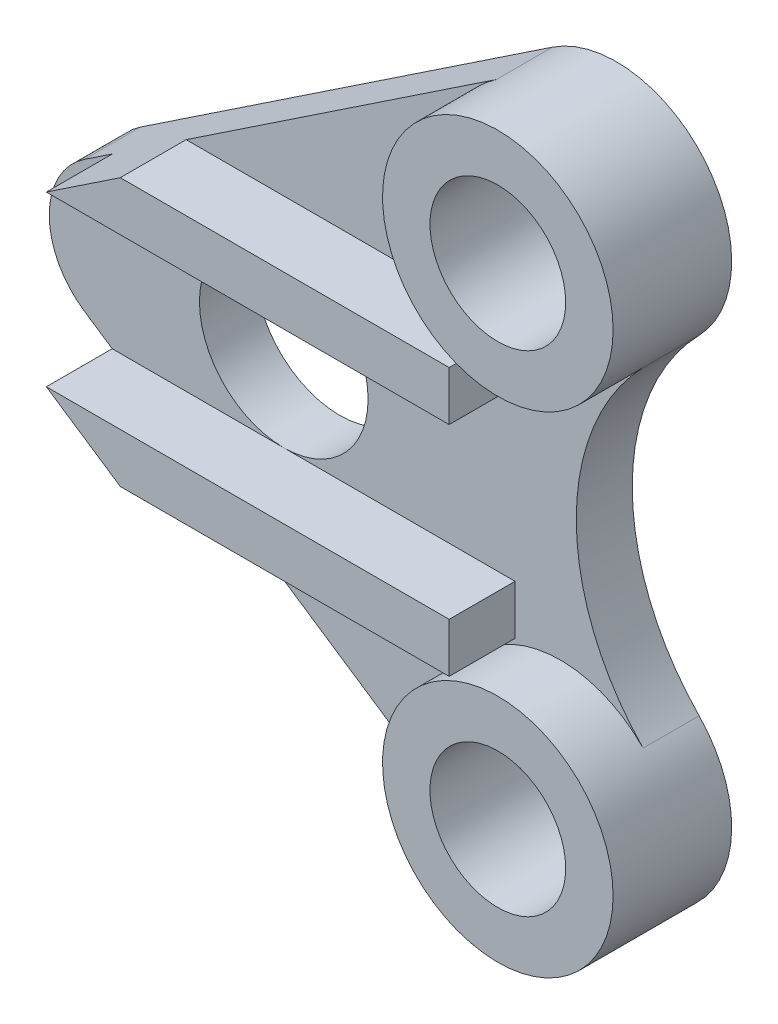
SolidWorks part; units mm, degrees
ref_plane "Front Plane" through (0, 0, 0) normal (0, 0, 1) x (1, 0, 0)
ref_plane "Top Plane" through (0, 0, 0) normal (0, 1, 0) x (1, 0, 0)
ref_plane "Right Plane" through (0, 0, 0) normal (1, 0, 0) x (0, 0, -1)
sketch "Sketch1" plane through (0, 0, 0) normal (0, 0, 1) x (1, 0, 0)
  line L0 (0, 5.1219) -> (0, -5.1219) construction
  line L1 (0, 0) -> (13.2766, 0) construction
  line L2 (8.1971, 13.145) -> (-7.6874, 2.5346)
  line L3 (-7.6874, -2.5346) -> (8.1971, -13.145)
  circle A0 centre (0, 0) radius 3.2512
  circle A1 centre (-5.9944, 0) radius 1.4732 construction
  circle A2 centre (5.9944, 0) radius 1.4732 construction
  circle A3 centre (10.6661, 9.4488) radius 2.6162
  circle A4 centre (10.6661, -9.4488) radius 2.6162
  arc A5 (-7.6874, 2.5346) -> (-7.6874, -2.5346) centre (-5.9944, 0) ccw
  arc A6 (8.1971, -13.145) -> (13.8546, -6.3518) centre (10.6661, -9.4488) ccw
  arc A7 (13.8546, 6.3518) -> (8.1971, 13.145) centre (10.6661, 9.4488) ccw
  arc A8 (13.8546, 6.3518) -> (13.8546, -6.3518) centre (20.3941, 0) ccw
  point P9 (0, 0)
  dimension "D1" = 2.9464
  dimension "D2" = 6.5024
  dimension "D3" = 9.0424
  dimension "D4" = 5.2324
  dimension "D5" = 18.8976
  dimension "D6" = 8.382
  dimension "D7" = 4.445
  dimension "D8" = 3.048
  dimension "D9" = 3.81
extrude "Boss-Extrude1" add sketch "Sketch1" along normal blind 4.572
sketch "Sketch2" plane through (0, 0, 4.572) normal (0, 0, 1) x (1, 0, 0)
  line L2 (8.1971, 13.145) -> (-7.6874, 2.5346)
  line L3 (-7.6874, -2.5346) -> (8.1971, -13.145)
  line L4 (8.1971, 13.145) -> (-7.6874, 2.5346)
  line L5 (-7.6874, -2.5346) -> (8.1971, -13.145)
  arc A0 (8.1971, 13.145) -> (13.8546, 6.3518) centre (10.6661, 9.4488) ccw
  arc A1 (13.8546, -6.3518) -> (8.1971, -13.145) centre (10.6661, -9.4488) ccw
  arc A4 (13.8546, 6.3518) -> (8.1971, 13.145) centre (10.6661, 9.4488) ccw
  arc A5 (-7.6874, 2.5346) -> (-7.6874, -2.5346) centre (-5.9944, 0) ccw
  arc A6 (8.1971, -13.145) -> (13.8546, -6.3518) centre (10.6661, -9.4488) ccw
  arc A7 (13.8546, 6.3518) -> (13.8546, -6.3518) centre (20.3941, 0) ccw
  arc A9 (-7.6874, 2.5346) -> (-7.6874, -2.5346) centre (-5.9944, 0) ccw
  arc A11 (13.8546, 6.3518) -> (13.8546, -6.3518) centre (20.3941, 0) ccw
  dimension "D1" = 0
extrude "Cut-Extrude2" cut sketch "Sketch2" against normal offset from surface (2.413 mm away) 2.159 up to face at (5.1514, 0, 0)
sketch "Sketch3" plane through (0, 0, 2.159) normal (0, 0, 1) x (1, 0, 0)
  line L0 (-7.6874, 2.5346) -> (8.1971, 13.145) construction
  line L1 (-3.7627, 5.1562) -> (8.9166, 5.1562)
  line L3 (-3.7627, 3.2512) -> (8.9166, 3.2512)
  line L4 (8.9166, 5.1562) -> (8.9166, 3.2512)
  line L5 (8.1971, -13.145) -> (-7.6874, -2.5346) construction
  line L6 (-3.7627, -3.2512) -> (8.9166, -3.2512)
  line L8 (-3.7627, -5.1562) -> (8.9166, -5.1562)
  line L9 (8.9166, -3.2512) -> (8.9166, -5.1562)
  line L10 (-3.7627, 5.1562) -> (-6.6146, 3.2512)
  line L11 (-6.6146, 3.2512) -> (-3.7627, 3.2512)
  line L12 (-3.7627, -3.2512) -> (-6.6146, -3.2512)
  line L13 (-6.6146, -3.2512) -> (-3.7627, -5.1562)
  circle A1 centre (0, 0) radius 3.2512 construction
  dimension "D1" = 1.905
  dimension "D2" = 1.905
  dimension "D3" = 1.905
  dimension "D4" = 1.905
extrude "Boss-Extrude2" add sketch "Sketch3" along normal blind 2.54
